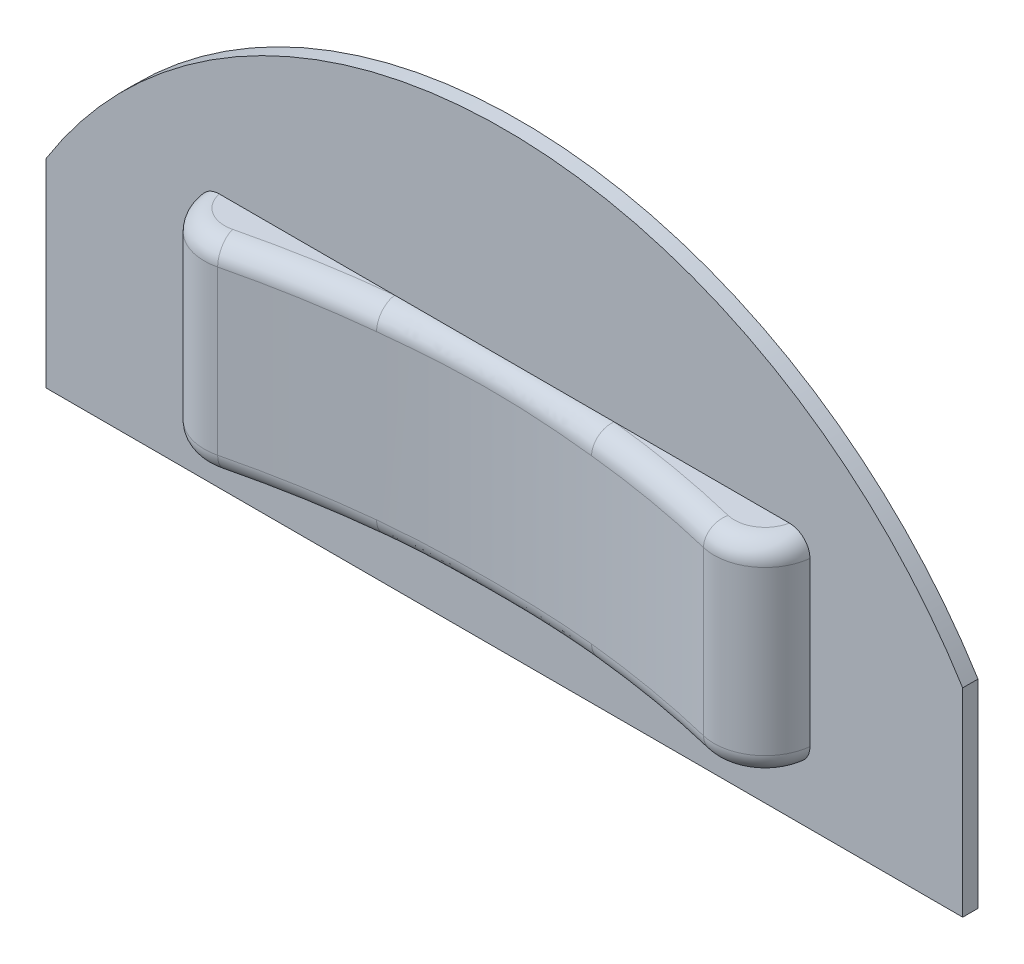
SolidWorks part; units mm, degrees
ref_plane "Front Plane" through (0, 0, 0) normal (0, 0, 1) x (1, 0, 0)
ref_plane "Top Plane" through (0, 0, 0) normal (0, 1, 0) x (1, 0, 0)
ref_plane "Right Plane" through (0, 0, 0) normal (1, 0, 0) x (0, 0, -1)
sketch "Sketch1" plane through (0, 0, 0) normal (0, 0, 1) x (1, 0, 0)
  line L0 (180, 0) -> (180, -39)
  line L1 (0, 0) -> (0, -39)
  line L2 (0, -39) -> (180, -39)
  arc A0 (0, 0) -> (180, 0) centre (90, -56) cw
  point P3 (90, 50)
  dimension "D1" = 50
  dimension "D2" = 39
  dimension "D3" = 39
  dimension "D4" = 180
extrude "Boss-Extrude1" add sketch "Sketch1" along normal blind 3 contours L2 L0 A0 L1
sketch "Sketch2" plane through (0, 0, 3) normal (0, 0, 1) x (1, 0, 0)
  line L0 (0, -39) -> (180, -39) construction
  line L1 (30, 11) -> (150, 11)
  line L2 (30, 11) -> (30, -29)
  line L3 (30, -29) -> (150, -29)
  line L4 (150, 11) -> (150, -29)
  line L5 (180, 0) -> (180, -39) construction
  line L6 (0, 0) -> (0, -39) construction
  dimension "D1" = 10
  dimension "D2" = 30
  dimension "D3" = 30
  dimension "D4" = 40
extrude "Boss-Extrude2" add sketch "Sketch2" along normal blind 12
sketch "Sketch3" plane through (0, 11, 0) normal (0, 1, 0) x (1, 0, 0)
  line L0 (150, -15) -> (150, -3) construction
  line L1 (150, -15) -> (30, -15) construction
  line L2 (30, -15) -> (150, -15)
  arc A0 (30, -15) -> (150, -15) centre (90, -207.6038) cw
extrude "Cut-Extrude1" cut sketch "Sketch3" against normal up to next
fillet "Fillet1" radius 10 2 edges at (150, -9, 15) (30, -9, 15)
fillet "Fillet2" radius 4 6 edges at (145.7894, -29, 10.073) (90, -29, 5.8708) (34.2106, -29, 10.073) (145.7894, 11, 10.073) (90, 11, 5.8708) (34.2106, 11, 10.073)
